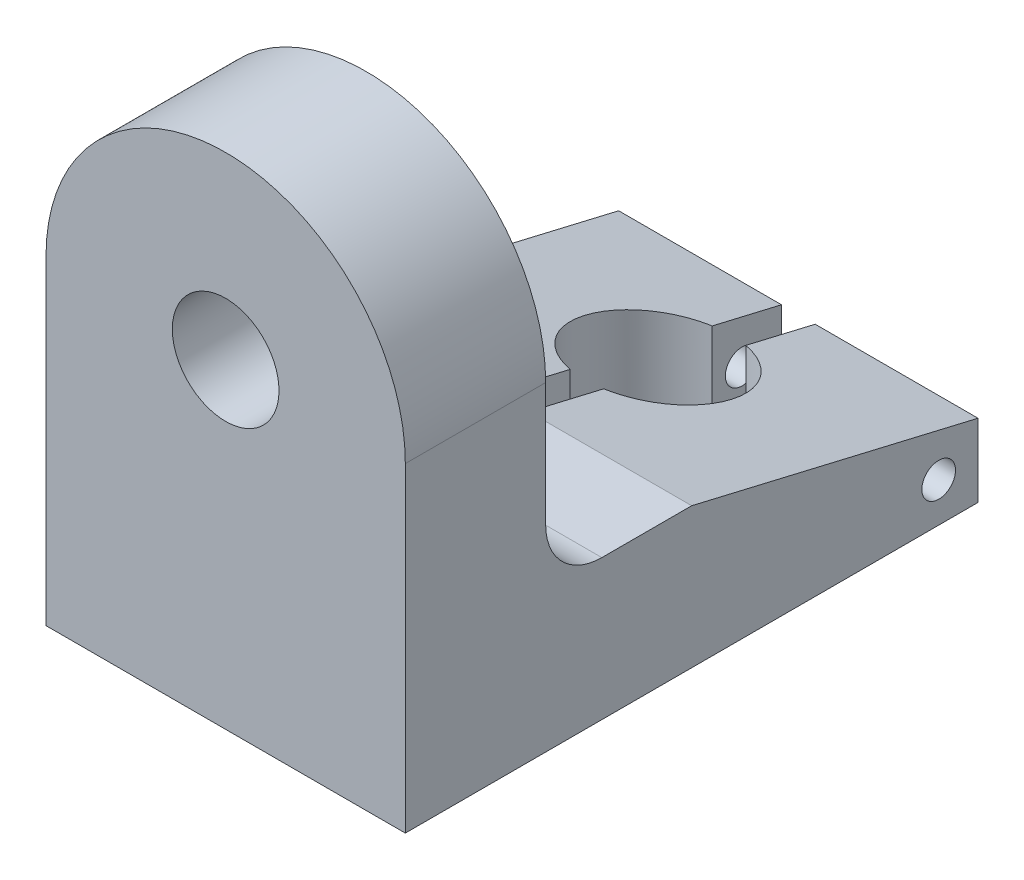
SolidWorks part; units mm, degrees
ref_plane "Piano frontale" through (0, 0, 0) normal (0, 0, 1) x (1, 0, 0)
ref_plane "Piano superiore" through (0, 0, 0) normal (0, 1, 0) x (1, 0, 0)
ref_plane "Piano destro" through (0, 0, 0) normal (1, 0, 0) x (0, 0, -1)
sketch "Schizzo1" plane through (0, 0, 0) normal (1, 0, 0) x (0, 0, -1)
  line L0 (0, 0) -> (77, 0)
  line L1 (77, 0) -> (77, -25)
  line L2 (77, -25) -> (-25, -25)
  line L3 (-25, -25) -> (-25, 64)
  line L4 (-25, 64) -> (0, 64)
  line L5 (0, 64) -> (0, 0)
  dimension "D1" = 102
  dimension "D2" = 89
  dimension "D3" = 25
  dimension "D4" = 25
extrude "Estrusione-Estrusione1" add sketch "Schizzo1" against normal blind 64
fillet "Raccordo1" 2 edges at (0, 64, 12.5) (-64, 64, 12.5) type full round first side face at (0, 13, -17.3333) second side face at (-64, 13, -17.3333) middle face at (-32, 64, 12.5)
sketch "Schizzo2" plane through (0, 0, 0) normal (0, 1, 0) x (1, 0, 0)
  line L0 (0, 77) -> (0, 0) construction
  line L1 (-64, 77) -> (0, 77) construction
  line L2 (-32, 77) -> (-32, -7.6641) construction
  line L3 (-29, 77) -> (-35, 77)
  line L4 (-35, 77) -> (-35, 13)
  line L5 (-35, 13) -> (-29, 13)
  line L6 (-29, 77) -> (-29, 13)
  circle A0 centre (-32, 52) radius 13
  point P11 (0, 0)
  point P13 (-32, 13)
  point P14 (0, 0)
  dimension "D3" = 26
  dimension "D1" = 32
  dimension "D2" = 25
  dimension "D4" = 6
  dimension "D5" = 64
extrude "Taglio-Estrusione1" cut sketch "Schizzo2" against normal through all contours A0
sketch "Schizzo5" plane through (0, 0, 0) normal (0, 1, 0) x (1, 0, 0)
  line L0 (-32, 77) -> (-32, -51) construction
  line L1 (-64, 77) -> (0, 77) construction
  line L2 (-29, 77) -> (-35, 77)
  line L3 (-35, 77) -> (-35, 13)
  line L4 (-35, 13) -> (-29, 13)
  line L5 (-29, 77) -> (-29, 13)
  point P8 (-32, 13)
  dimension "D1" = 6
  dimension "D2" = 64
extrude "Taglio-Estrusione2" cut sketch "Schizzo5" against normal through all
sketch "Schizzo6" plane through (0, 0, 0) normal (1, 0, 0) x (0, 0, -1)
  line L0 (26, 0) -> (77, -12)
  line L1 (77, 0) -> (0, 0) construction
  line L2 (77, -25) -> (77, 0) construction
  line L3 (77, -12) -> (77, 0)
  line L4 (77, 0) -> (26, 0)
  dimension "D1" = 51
  dimension "D2" = 12
extrude "Taglio-Estrusione3" cut sketch "Schizzo6" against normal through all
sketch "Schizzo7" plane through (0, 0, 0) normal (1, 0, 0) x (0, 0, -1)
  line L0 (-25, -25) -> (77, -25) construction
  line L1 (77, -25) -> (77, -12) construction
  circle A0 centre (70, -18) radius 3
  dimension "D3" = 6
  dimension "D1" = 7
  dimension "D2" = 7
extrude "Taglio-Estrusione4" cut sketch "Schizzo7" against normal through all
sketch "Schizzo8" plane through (0, 0, 0) normal (0, 0, -1) x (-1, 0, 0)
  line L0 (64, 0) -> (64, 32) construction
  circle A0 centre (32, 32) radius 12.5
  arc A1 (64, 32) -> (0, 32) centre (32, 32) ccw construction
  dimension "D3" = 25
  dimension "D1" = 32
  dimension "D2" = 0
extrude "Estrusione-Estrusione2" add sketch "Schizzo8" along normal blind 5
sketch "Schizzo9" plane through (0, 0, -5) normal (0, 0, -1) x (-1, 0, 0)
  circle A0 centre (32, 32) radius 9.5
  circle A1 centre (32, 32) radius 12.5 construction
  dimension "D1" = 19
extrude "Taglio-Estrusione5" cut sketch "Schizzo9" against normal through all
fillet "Raccordo2" radius 10 1 edges at (-32, 0, 0)
fillet "Raccordo3" radius 5 1 edges at (-44.5, 32, 0)
